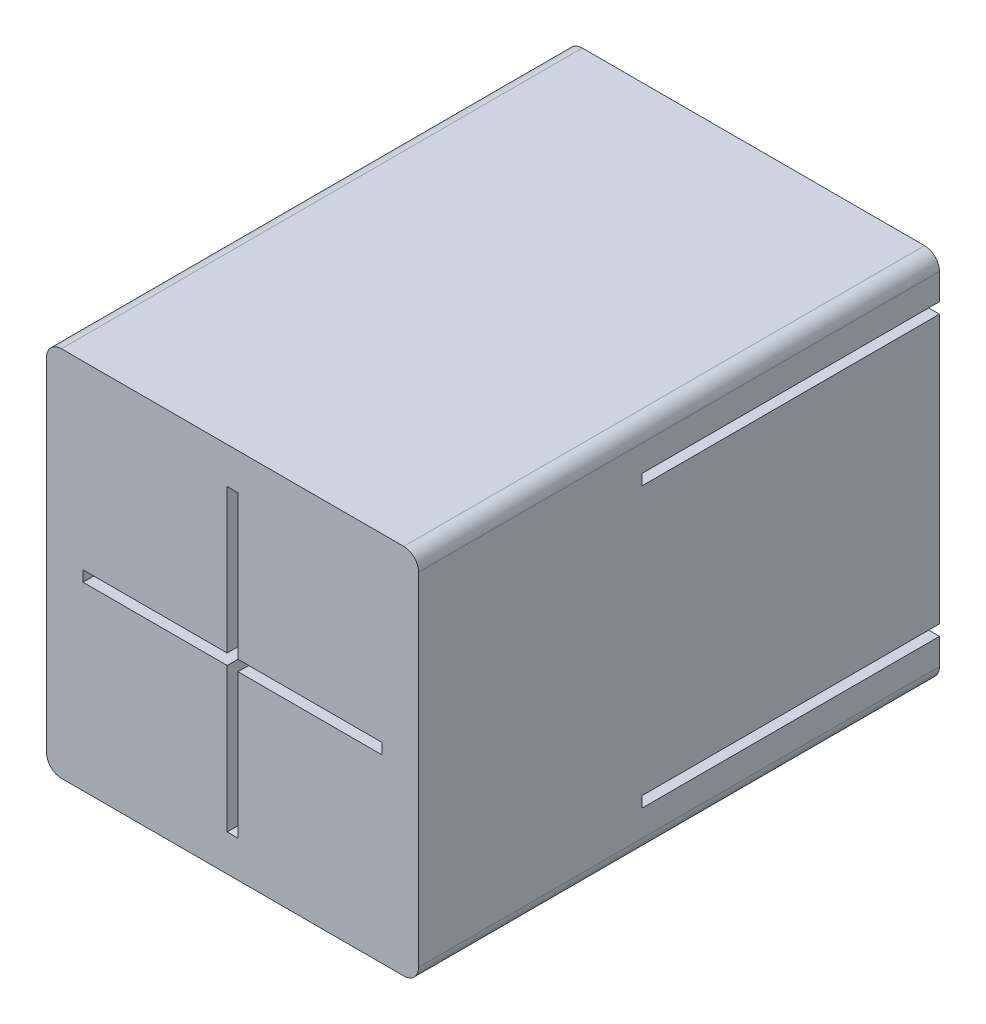
SolidWorks part; units mm, degrees
ref_plane "Front" through (0, 0, 0) normal (0, 0, 1) x (1, 0, 0)
ref_plane "Top" through (0, 0, 0) normal (0, 1, 0) x (1, 0, 0)
ref_plane "Right" through (0, 0, 0) normal (1, 0, 0) x (0, 0, -1)
sketch "Sketch1" plane through (0, 0, 0) normal (0, 0, 1) x (1, 0, 0)
  line L0 (-25.527, -0.9207) -> (25.527, -0.9208)
  line L1 (-31.75, -31.75) -> (31.75, -31.75)
  line L2 (-31.75, -31.75) -> (-31.75, 31.75)
  line L3 (-31.75, 31.75) -> (31.75, 31.75)
  line L4 (31.75, -31.75) -> (31.75, 31.75)
  line L5 (-0.9208, -25.527) -> (0.9208, -25.527)
  line L6 (-0.9208, -25.527) -> (-0.9207, 25.527)
  line L11 (-0.9207, 25.527) -> (0.9208, 25.527)
  line L12 (0.9208, -25.527) -> (0.9208, 25.527)
  line L13 (0, 25.527) -> (0, -25.527) construction
  line L14 (-0.9207, 0) -> (0.9208, 0) construction
  line L15 (-25.527, 0.9208) -> (25.527, 0.9207)
  line L16 (25.527, 0.9207) -> (25.527, -0.9208)
  line L17 (-25.527, 0.9208) -> (-25.527, -0.9207)
  line L18 (-0.9207, 25.527) -> (-0.9208, -25.527)
  line L19 (0.9208, 25.527) -> (0.9207, -25.527)
  line L20 (0.9207, -25.527) -> (-0.9208, -25.527)
  line L33 (0.9208, 25.527) -> (-0.9207, 25.527)
  line L35 (31.75, 31.75) -> (31.75, -31.75)
  line L38 (25.527, 0.9207) -> (-25.527, 0.9208)
  line L39 (25.527, -0.9208) -> (-25.527, -0.9207)
  line L41 (-31.75, 31.75) -> (-31.75, -31.75)
  line L42 (-25.527, -0.9207) -> (-25.527, 0.9208)
  line L43 (25.527, -0.9208) -> (25.527, 0.9207)
  point P0 (0, 0)
  point P22 (0, 0)
  dimension "D1" = 63.5
  dimension "D2" = 1.8415
  dimension "D3" = 51.054
  dimension "D4" = 4
extrude "Boss-Extrude1" add sketch "Sketch1" along normal blind 25.4 contours L1 L4 L3 L2 region at (-30.852, 0, 0)
extrude "Boss-Extrude2" add sketch "Sketch1<7>" against normal blind 63.5
sketch "Sketch1<7>" plane through (0, 0, 0) normal (0, 0, 1) x (1, 0, 0) same geometry as "Sketch1"
sketch "Sketch2" plane through (-31.75, 0, 0) normal (-1, 0, 0) x (0, 0, 1)
  line L0 (25.4, -31.75) -> (-63.5, -31.75) construction
  line L1 (-63.5, 31.75) -> (-12.7, 31.75) construction
  line L3 (-63.5, -31.75) -> (-12.7, -31.75) construction
  line L5 (-63.5, -15.875) -> (-12.7, -15.875)
  line L6 (-63.5, 31.75) -> (-12.7, 31.75)
  line L8 (-12.7, 31.75) -> (-63.5, 31.75)
  line L10 (-12.7, 0) -> (-63.5, 0)
  line L12 (-12.7, 31.75) -> (-63.5, 0) construction
  line L13 (-12.7, 0) -> (-63.5, 31.75) construction
  line L14 (-12.7, -31.75) -> (-63.5, -31.75)
  line L15 (-12.7, -31.75) -> (-12.7, 0)
  line L16 (-12.7, 0) -> (-63.5, 0)
  line L18 (-12.7, -31.75) -> (-63.5, 0) construction
  line L19 (-12.7, 0) -> (-63.5, -31.75) construction
  line L20 (-63.5, 15.875) -> (-12.7, 15.875)
  line L22 (-63.5, 31.75) -> (-12.7, 15.875) construction
  line L23 (-63.5, 15.875) -> (-12.7, 31.75) construction
  line L24 (-12.7, -31.75) -> (-12.7, -15.875)
  line L25 (-63.5, -31.75) -> (-12.7, -31.75)
  line L27 (-63.5, -15.875) -> (-12.7, -31.75) construction
  line L28 (-63.5, -31.75) -> (-12.7, -15.875) construction
  line L29 (-12.7, -22.8917) -> (-12.7, -24.7332)
  line L30 (-63.5, 22.8917) -> (-12.7, 22.8917)
  line L31 (-63.5, 22.8917) -> (-63.5, 24.7332)
  line L32 (-63.5, 24.7332) -> (-12.7, 24.7332)
  line L33 (-12.7, 22.8917) -> (-12.7, 24.7332)
  line L34 (-38.1, 24.7332) -> (-38.1, 22.8917) construction
  line L35 (-63.5, 23.8125) -> (-12.7, 23.8125) construction
  line L36 (-63.5, -24.7332) -> (-12.7, -24.7332)
  line L37 (-63.5, -22.8918) -> (-12.7, -22.8917)
  line L38 (-63.5, -22.8918) -> (-63.5, -24.7332)
  point P4 (-38.1, 0)
  point P10 (-38.1, 15.875)
  point P12 (-38.1, -15.875)
  point P14 (-38.1, 23.8125)
  point P17 (-38.1, -23.8125)
  point P18 (-38.1, 23.8125)
  line M14 (-63.5, 31.75) -> (-63.5, -31.75)
  dimension "D1" = 50.8
  dimension "D2" = 1.8415
extrude "Cut-Extrude1" cut sketch "Sketch2" against normal through all from offset 6.35 contours L30 L33 L32 M14 | L37 L29 L36 L38 region at (-31.75, 23.8125, -38.1) offset against normal yes
fillet "Fillet1" radius 2.54 4 edges at (31.75, 31.75, -19.05) (31.75, -31.75, -19.05) (-31.75, -31.75, -19.05) (-31.75, 31.75, -19.05)
